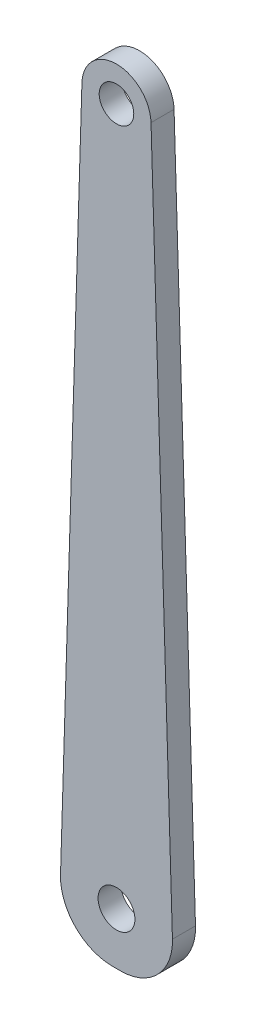
SolidWorks part; units mm, degrees
material "1.0044 (S275JR)"
ref_plane "Plan de face" through (0, 0, 0) normal (0, 0, 1) x (1, 0, 0)
ref_plane "Plan de dessus" through (0, 0, 0) normal (0, 1, 0) x (1, 0, 0)
ref_plane "Plan de droite" through (0, 0, 0) normal (1, 0, 0) x (0, 0, -1)
sketch "Esquisse1" plane through (0, 0, 0) normal (0, 0, 1) x (1, 0, 0)
  line L0 (0, 0) -> (100, 0)
  line L1 (100, 0) -> (79.9858, 650.922)
  line L2 (0, 0) -> (20.0142, 650.922)
  arc A0 (79.9858, 650.922) -> (20.0142, 650.922) centre (50, 650) ccw
  circle A1 centre (50, 650) radius 15
  dimension "D2" = 650
  dimension "D3" = 60
  dimension "D5" = 30
  dimension "D1" = 100
  dimension "D4" = 50
base flange "Tôle de base pliée1" sketch "Esquisse1" thickness 20 reverse thickness direction no parameters "D1"=5
sketch "Esquisse6" plane through (0, 0, 0) normal (0, 0, 1) x (1, 0, 0)
  circle A0 centre (50, 45) radius 16
  dimension "D1" = 32
  dimension "D2" = 50
  dimension "D3" = 45
extrude "Enlèv. mat.-Extru.1" cut sketch "Esquisse6" against normal through all normal cut yes
fillet "Congé4" radius 45 2 edges at (100, 0, -10) (0, 0, -10)
sketch "Lignes de pliage1" [suppressed] plane through (0, 0, 0) normal (0, 1, 0) x (1, 0, 0)
sketch "Cube de visualisation1" [suppressed] plane through (0, 0, 0) normal (0, 1, 0) x (1, 0, 0)
sheet metal parameters "Tôlerie1" thickness 20 parameters "D1"=5
flat pattern "Etat déplié1" [suppressed]
sketch "Lignes de pliage2" plane through (0, 0, 0) normal (0, 1, 0) x (1, 0, 0)
sketch3d "Cube de visualisation2" [suppressed]
  line L0 (29.2412, 30.74, 0) -> (49.9713, -798.8513, 0) construction
  line L1 (-68.3996, 28.3002, 0) -> (-47.6695, -801.2911, 0) construction
  line L2 (29.2412, 30.74, 0) -> (-68.3996, 28.3002, 0) construction
  line L3 (49.9713, -798.8513, 0) -> (-47.6695, -801.2911, 0) construction
sheet metal parameters "Tôlerie2" thickness 20 parameters "D1"=5
flat pattern "Etat déplié1"
sketch "Lignes de pliage2" plane through (0, 0, 0) normal (0, 1, 0) x (1, 0, 0)
sketch3d "Cube de visualisation2" [suppressed]
  line L0 (47.9748, -901.1654, 0) -> (68.6261, 28.4829, 0) construction
  line L1 (-49.9776, -898.9895, 0) -> (-29.3263, 30.6589, 0) construction
  line L2 (47.9748, -901.1654, 0) -> (-49.9776, -898.9895, 0) construction
  line L3 (68.6261, 28.4829, 0) -> (-29.3263, 30.6589, 0) construction
